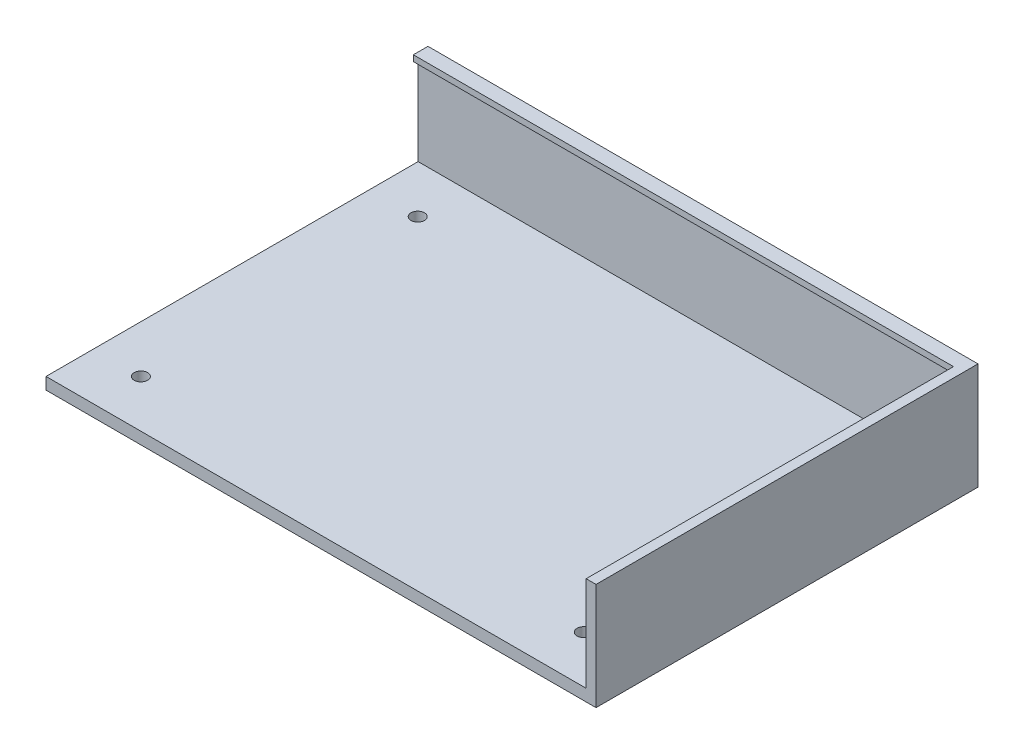
SolidWorks part; units mm, degrees
ref_plane "Front Plane" through (0, 0, 0) normal (0, 0, 1) x (1, 0, 0)
ref_plane "Top Plane" through (0, 0, 0) normal (0, 1, 0) x (1, 0, 0)
ref_plane "Right Plane" through (0, 0, 0) normal (1, 0, 0) x (0, 0, -1)
sketch "Sketch1" plane through (0, 0, 0) normal (0, 1, 0) x (1, 0, 0)
  line L1 (-139.1, -96.6) -> (139.1, -96.6)
  line L2 (-139.1, -96.6) -> (-139.1, 96.6)
  line L3 (-139.1, 96.6) -> (139.1, 96.6)
  line L4 (139.1, -96.6) -> (139.1, 96.6)
  line L5 (-139.1, -96.6) -> (139.1, 96.6) construction
  line L6 (-139.1, 96.6) -> (139.1, -96.6) construction
  point P0 (0, 0)
  dimension "D1" = 278.2
  dimension "D2" = 193.2
extrude "Shell Block" add sketch "Sketch1" along normal blind 27
ref_plane "Shell Front" through (0, 27, 0) normal (0, 1, 0) x (1, 0, 0)
sketch "Sketch2" plane through (0, 27, 0) normal (0, 1, 0) x (1, 0, 0)
  line L1 (-136.6, -92.9) -> (136.6, -92.9)
  line L2 (-136.6, -92.9) -> (-136.6, 92.9)
  line L3 (-136.6, 92.9) -> (136.6, 92.9)
  line L4 (136.6, -92.9) -> (136.6, 92.9)
  line L5 (-136.6, -92.9) -> (136.6, 92.9) construction
  line L6 (-136.6, 92.9) -> (136.6, -92.9) construction
  point P0 (0, 0)
  dimension "D1" = 273.2
  dimension "D2" = 185.8
extrude "Front Opening" cut sketch "Sketch2" against normal blind 1.5
ref_plane "Under Lip" through (0, 25.5, 0) normal (0, 1, 0) x (1, 0, 0)
sketch "Sketch3" plane through (0, 25.5, 0) normal (0, 1, 0) x (1, 0, 0)
  line L1 (-136.6, -94.1) -> (136.6, -94.1)
  line L2 (-136.6, -94.1) -> (-136.6, 94.1)
  line L3 (-136.6, 94.1) -> (136.6, 94.1)
  line L4 (136.6, -94.1) -> (136.6, 94.1)
  line L5 (-136.6, -94.1) -> (136.6, 94.1) construction
  line L6 (-136.6, 94.1) -> (136.6, -94.1) construction
  point P0 (0, 0)
  dimension "D1" = 273.2
  dimension "D2" = 188.2
extrude "Display Pocket" cut sketch "Sketch3" against normal blind 22.5
ref_plane "Back Inner" through (0, 3, 0) normal (0, 1, 0) x (1, 0, 0)
sketch "Sketch4" plane through (0, 3, 0) normal (0, 1, 0) x (1, 0, 0)
  line L1 (-69, 28) -> (-66, 28)
  line L2 (-69, 28) -> (-69, 84)
  line L3 (-69, 84) -> (-66, 84)
  line L4 (-66, 28) -> (-66, 84)
  line L6 (-69, -84) -> (-66, -84)
  line L7 (-69, -84) -> (-69, -28)
  line L8 (-69, -28) -> (-66, -28)
  line L9 (-66, -84) -> (-66, -28)
  line L11 (-77, 28) -> (-74, 28)
  line L12 (-77, 28) -> (-77, 84)
  line L13 (-77, 84) -> (-74, 84)
  line L14 (-74, 28) -> (-74, 84)
  line L16 (-77, -84) -> (-74, -84)
  line L17 (-77, -84) -> (-77, -28)
  line L18 (-77, -28) -> (-74, -28)
  line L19 (-74, -84) -> (-74, -28)
  line L21 (-85, 28) -> (-82, 28)
  line L22 (-85, 28) -> (-85, 84)
  line L23 (-85, 84) -> (-82, 84)
  line L24 (-82, 28) -> (-82, 84)
  line L26 (-85, -84) -> (-82, -84)
  line L27 (-85, -84) -> (-85, -28)
  line L28 (-85, -28) -> (-82, -28)
  line L29 (-82, -84) -> (-82, -28)
  line L31 (-93, 28) -> (-90, 28)
  line L32 (-93, 28) -> (-93, 84)
  line L33 (-93, 84) -> (-90, 84)
  line L34 (-90, 28) -> (-90, 84)
  line L36 (-93, -84) -> (-90, -84)
  line L37 (-93, -84) -> (-93, -28)
  line L38 (-93, -28) -> (-90, -28)
  line L39 (-90, -84) -> (-90, -28)
  line L41 (-101, 28) -> (-98, 28)
  line L42 (-101, 28) -> (-101, 84)
  line L43 (-101, 84) -> (-98, 84)
  line L44 (-98, 28) -> (-98, 84)
  line L46 (-101, -84) -> (-98, -84)
  line L47 (-101, -84) -> (-101, -28)
  line L48 (-101, -28) -> (-98, -28)
  line L49 (-98, -84) -> (-98, -28)
  line L51 (-109, 28) -> (-106, 28)
  line L52 (-109, 28) -> (-109, 84)
  line L53 (-109, 84) -> (-106, 84)
  line L54 (-106, 28) -> (-106, 84)
  line L56 (-109, -84) -> (-106, -84)
  line L57 (-109, -84) -> (-109, -28)
  line L58 (-109, -28) -> (-106, -28)
  line L59 (-106, -84) -> (-106, -28)
  line L61 (-117, 28) -> (-114, 28)
  line L62 (-117, 28) -> (-117, 84)
  line L63 (-117, 84) -> (-114, 84)
  line L64 (-114, 28) -> (-114, 84)
  line L66 (-117, -84) -> (-114, -84)
  line L67 (-117, -84) -> (-117, -28)
  line L68 (-117, -28) -> (-114, -28)
  line L69 (-114, -84) -> (-114, -28)
  line L71 (-125, 28) -> (-122, 28)
  line L72 (-125, 28) -> (-125, 84)
  line L73 (-125, 84) -> (-122, 84)
  line L74 (-122, 28) -> (-122, 84)
  line L76 (-125, -84) -> (-122, -84)
  line L77 (-125, -84) -> (-125, -28)
  line L78 (-125, -28) -> (-122, -28)
  line L79 (-122, -84) -> (-122, -28)
extrude "Vent Slots" cut sketch "Sketch4" against normal blind 4
sketch "Sketch5" plane through (0, 0, 0) normal (1, 0, 0) x (0, 0, -1)
  line L1 (-29, 5) -> (29, 5)
  line L2 (-29, 5) -> (-29, 28)
  line L3 (-29, 28) -> (29, 28)
  line L4 (29, 5) -> (29, 28)
extrude "Cable Exit (-X short side)" cut sketch "Sketch5" against normal blind 140.1
sketch "Sketch6" plane through (0, 3, 0) normal (0, 1, 0) x (1, 0, 0)
  circle A0 centre (-40, -29) radius 1.7
  circle A1 centre (-40, -89) radius 1.7
  circle A2 centre (40, -29) radius 1.7
  circle A3 centre (40, -89) radius 1.7
  circle A4 centre (-52, -47) radius 1.7
  circle A5 centre (-52, -71) radius 1.7
  circle A6 centre (52, -47) radius 1.7
  circle A7 centre (52, -71) radius 1.7
  circle A8 centre (-12, 82) radius 1.7
  circle A9 centre (12, 82) radius 1.7
  circle A10 centre (124, 12) radius 1.7
  circle A11 centre (124, -12) radius 1.7
  circle A12 centre (-12, 12) radius 1.7
  circle A13 centre (-12, -12) radius 1.7
  circle A14 centre (12, 12) radius 1.7
  circle A15 centre (12, -12) radius 1.7
  circle A16 centre (-110, -12) radius 1.7
  circle A17 centre (-110, 12) radius 1.7
  circle A18 centre (-86, -12) radius 1.7
  circle A19 centre (-86, 12) radius 1.7
extrude "Bolt Holes" cut sketch "Sketch6" against normal blind 4
sketch "Sketch7" plane through (0, 0, 0) normal (0, 1, 0) x (1, 0, 0)
  line L1 (-200, -200) -> (0, -200)
  line L2 (-200, -200) -> (-200, 200)
  line L3 (-200, 200) -> (0, 200)
  line L4 (0, -200) -> (0, 200)
extrude "Keep one half (X)" cut sketch "Sketch7" against normal through all and the other way through all
sketch "Sketch8" plane through (0, 0, 0) normal (0, 1, 0) x (1, 0, 0)
  line L1 (-200, 0) -> (200, 0)
  line L2 (-200, 0) -> (-200, -200)
  line L3 (-200, -200) -> (200, -200)
  line L4 (200, 0) -> (200, -200)
extrude "Keep one quarter (Z)" cut sketch "Sketch8" against normal through all and the other way through all
equation "\"DispL\"= 272.0"
equation "\"DispW\"= 187.0"
equation "\"DispT\"= 20.0"
equation "\"Clr\"= 0.6"
equation "\"Wall\"= 2.5"
equation "\"BackT\"= 3.0"
equation "\"CableRoom\"= 4.0"
equation "\"LipW\"= 1.2"
equation "\"LipT\"= 1.5"
equation "\"CableW\"= 58.0"
equation "\"CableH\"= 16.0"
equation "\"BoltD\"= 3.4"
equation "\"ShellL\"= \"DispL\" + 2 * \"Clr\" + 2 * \"Wall\""
equation "\"ShellW\"= \"DispW\" + 2 * \"Clr\" + 2 * \"Wall\""
equation "\"ShellH\"= \"BackT\" + \"DispT\" + \"CableRoom\""
equation "\"D1@Sketch1\" = \"ShellL\""
equation "\"D2@Sketch1\" = \"ShellW\""
equation "\"D1@Shell Block\" = \"ShellH\""
equation "\"D1@Shell Front\" = \"ShellH\""
equation "\"D1@Sketch2\" = \"DispL\" + 2 * \"Clr\""
equation "\"D2@Sketch2\" = \"DispW\" + 2 * \"Clr\" - 2 * \"LipW\""
equation "\"D1@Front Opening\" = \"LipT\""
equation "\"D1@Under Lip\" = \"ShellH\" - \"LipT\""
equation "\"D1@Sketch3\" = \"DispL\" + 2 * \"Clr\""
equation "\"D2@Sketch3\" = \"DispW\" + 2 * \"Clr\""
equation "\"D1@Display Pocket\" = \"ShellH\" - \"LipT\" - \"BackT\""
equation "\"D1@Back Inner\" = \"BackT\""
